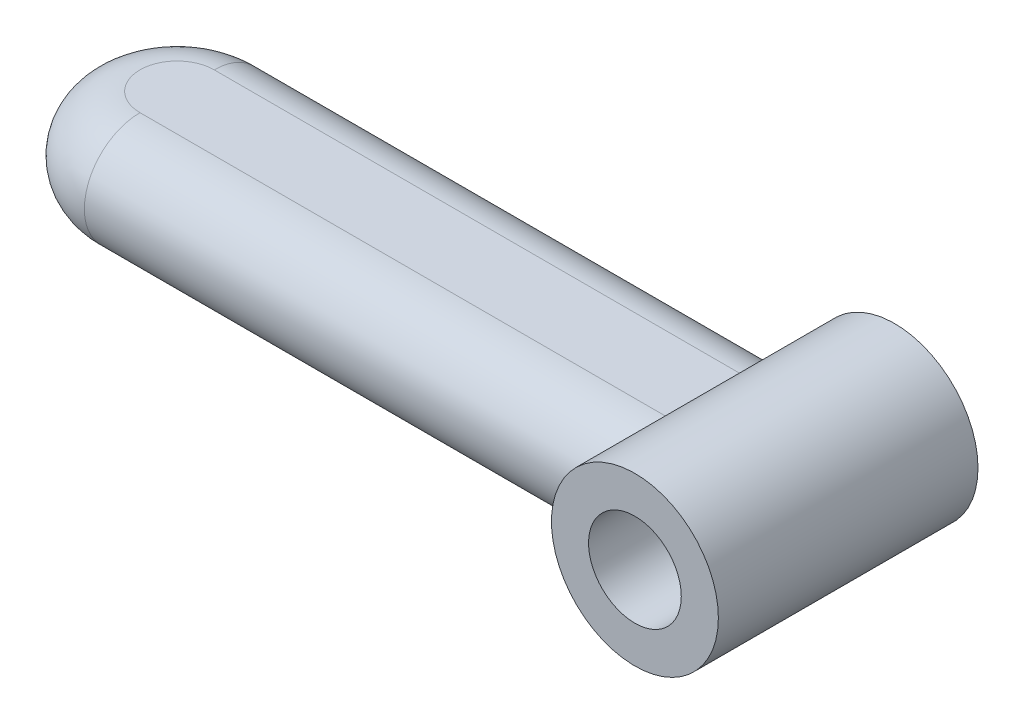
SolidWorks part; units mm, degrees
ref_plane "Front Plane" through (0, 0, 0) normal (0, 0, 1) x (1, 0, 0)
ref_plane "Top Plane" through (0, 0, 0) normal (0, 1, 0) x (1, 0, 0)
ref_plane "Right Plane" through (0, 0, 0) normal (1, 0, 0) x (0, 0, -1)
sketch "Sketch1" plane through (0, 0, 0) normal (0, 1, 0) x (1, 0, 0)
  line L1 (-16.6667, 5) -> (16.6667, 5)
  line L2 (-16.6667, 5) -> (-16.6667, -5)
  line L3 (-16.6667, -5) -> (16.6667, -5)
  line L4 (16.6667, 5) -> (16.6667, -5)
  point P4 (0, -5)
  point P6 (16.6667, 0)
  dimension "D1" = 33.3333
  dimension "D2" = 10
extrude "Boss-Extrude1" add sketch "Sketch1" along normal mid plane 6
fillet "Fillet1" 2 edges at (-16.6667, 0, 5) (-16.6667, 0, -5) type full round first side face at (0, 0, 5) second side face at (0, 0, -5) middle face at (-16.6667, 0, 0)
fillet "Fillet2" 2 edges at (2.5, 3, 5) (2.5, -3, 5) type full round first side face at (1.25, 3, 0) second side face at (1.25, -3, 0) middle face at (2.5, 0, 5)
ref_plane "Plane1" through (0, 0, 7) normal (0, 0, 1) x (1, 0, 0)
sketch "Sketch4" plane through (0, 0, 0) normal (0, 0, 1) x (1, 0, 0)
  circle A0 centre (20.0208, 0) radius 2.5
  circle A1 centre (20.0208, 0) radius 4.5
  dimension "D1" = 5
  dimension "D2" = 2
extrude "Boss-Extrude6" add sketch "Sketch4" along normal mid plane 14
sketch "Sketch5" plane through (0, 0, 0) normal (0, 1, 0) x (1, 0, 0)
  line L0 (15.5208, 7) -> (15.5208, 4.9999) construction
  line L1 (15.5208, 5.3852) -> (25.3736, 5.3852)
  line L2 (15.5208, 5.3852) -> (15.5208, -5.3852)
  line L3 (15.5208, -5.3852) -> (25.3736, -5.3852)
  line L4 (25.3736, 5.3852) -> (25.3736, -5.3852)
  point P5 (15.5208, 0)
